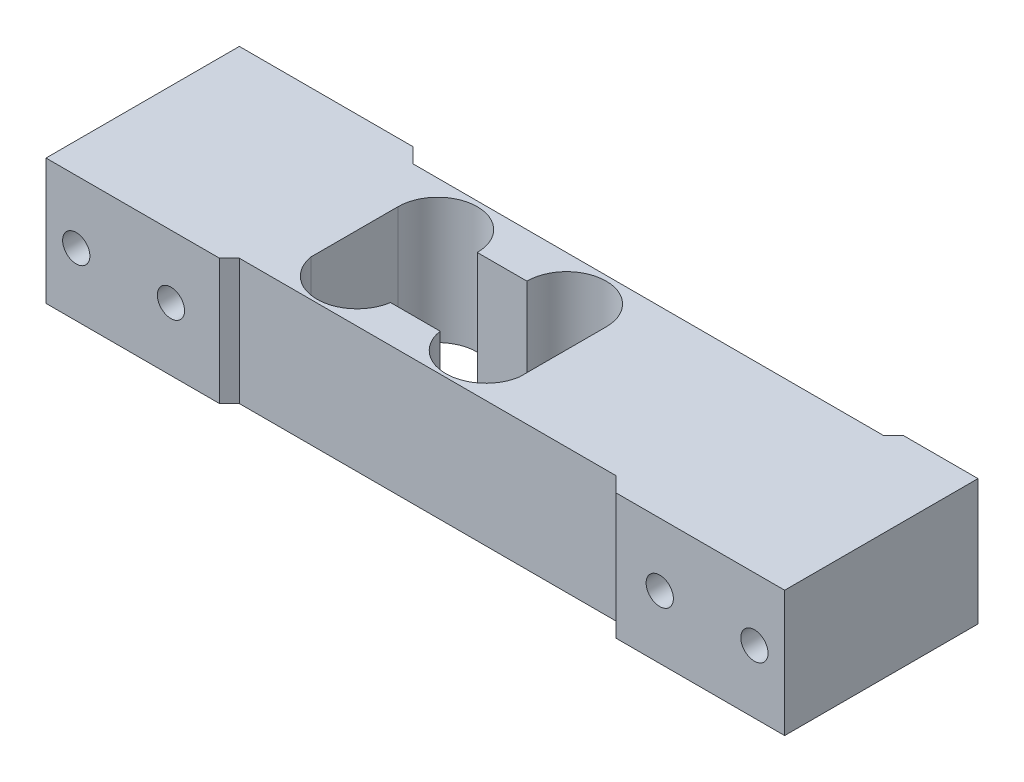
SolidWorks part; units mm, degrees
material "6063-T6"
ref_plane "Alzado" through (0, 0, 0) normal (0, 0, 1) x (1, 0, 0)
ref_plane "Planta" through (0, 0, 0) normal (0, 1, 0) x (1, 0, 0)
ref_plane "Vista lateral" through (0, 0, 0) normal (1, 0, 0) x (0, 0, -1)
sketch "Croquis1" plane through (0, 0, 0) normal (0, 1, 0) x (1, 0, 0)
  line L1 (-75, 20) -> (75, 20)
  line L2 (-75, 20) -> (-75, -20)
  line L3 (-75, -20) -> (75, -20)
  line L4 (75, 20) -> (75, -20)
  line L5 (-75, 20) -> (75, -20) construction
  line L6 (-75, -20) -> (75, 20) construction
  point P0 (0, 0)
  dimension "D1" = 40
  dimension "D2" = 150
extrude "Saliente-Extruir1" add sketch "Croquis1" along normal blind 25.4
sketch "Croquis2" plane through (0, 25.4, 0) normal (0, 1, 0) x (1, 0, 0)
  line L0 (-42, 20) -> (-42, 17)
  line L1 (75, 20) -> (-75, 20) construction
  line L2 (-42, 17) -> (61, 17)
  line L3 (61, 17) -> (61, 19)
  line L4 (60, 20) -> (-42, 20)
  line L5 (43, -20) -> (43, -17)
  line L6 (-75, -20) -> (75, -20) construction
  line L7 (43, -17) -> (-41, -17)
  line L8 (-41, -17) -> (-41, -19)
  line L9 (-41, -19) -> (-75, -19)
  line L10 (-75, 20) -> (-75, -20) construction
  line L11 (-75, -19) -> (-75, -20)
  line L12 (-75, -20) -> (43, -20)
  line L13 (75, -20) -> (75, 20) construction
  line L14 (61, 19) -> (75, 19)
  line L15 (75, 19) -> (75, 20)
  line L16 (75, 20) -> (60, 20)
  point P19 (-41, -18)
  dimension "D1" = 32
  dimension "D2" = 14
  dimension "D3" = 3
  dimension "D4" = 1
  dimension "D5" = 34
  dimension "D6" = 2
  dimension "D7" = 33
  dimension "D8" = 3
  dimension "D9" = 1
extrude "Cortar-Extruir1" cut sketch "Croquis2" against normal through all
chamfer "Chaflán1" distance 5 angle 45 2 edges at (43, 12.7, 17) (-42, 12.7, -17)
chamfer "Chaflán2" distance 3 angle 45 2 edges at (-41, 12.7, 17) (61, 12.7, -17)
sketch "Croquis3" plane through (0, 25.4, 0) normal (0, 1, 0) x (1, 0, 0)
  line L0 (-31, 17) -> (-31, -17) construction
  line L1 (-37, 17) -> (58, 17) construction
  line L2 (38, -17) -> (-38, -17) construction
  line L3 (11, 17) -> (11, -17) construction
  line L4 (-10, 17) -> (-10, -17) construction
  line L5 (-75, 20) -> (-75, -19) construction
  line L6 (-75, 8) -> (75, 8) construction
  line L7 (75, -20) -> (75, 19) construction
  line L8 (-75, -9.5) -> (75, -9.5) construction
  line L9 (-40, 20) -> (-75, 20) construction
  line L10 (-15, 8) -> (-5, 8)
  line L11 (-15, -9.5) -> (-5, -9.5)
  line L20 (-23, 8) -> (-23, -8.2527) construction
  line L22 (-31, 8) -> (-31, -9.5)
  line L23 (3, -8.2527) -> (3, 8) construction
  line L25 (11, -9.5) -> (11, 8)
  arc A0 (-15, 8) -> (-31, 8) centre (-23, 8) ccw
  arc A1 (-31, -9.5) -> (-15, -9.5) centre (-23, -8.2527) ccw
  arc A2 (-5, -9.5) -> (11, -9.5) centre (3, -8.2527) ccw
  arc A3 (11, 8) -> (-5, 8) centre (3, 8) ccw
  point P23 (-10, 8)
  point P26 (-10, -9.5)
  point P41 (-20.377, -0.75)
  point P48 (0.377, -0.75)
  dimension "D9" = 8
  dimension "D10" = 8
  dimension "D13" = 8.0966
  dimension "D1" = 65
  dimension "D2" = 86
  dimension "D3" = 44
  dimension "D4" = 12
  dimension "D5" = 17.5
  dimension "D6" = 10
  dimension "D7" = 5
  dimension "D8" = 5
  dimension "D11" = 16.2527
  dimension "D12" = 16.2527
extrude "Cortar-Extruir2" cut sketch "Croquis3" against normal through all
sketch "Croquis5" plane through (0, 0, -20) normal (0, 0, -1) x (-1, 0, 0)
  line L0 (75, 12.7) -> (40, 12.7) construction
  line L1 (75, 25.4) -> (75, 0) construction
  line L2 (40, 25.4) -> (40, 0) construction
  line L3 (68.9, 0) -> (68.9, 25.4) construction
  line L4 (40, 0) -> (75, 0) construction
  line L5 (40, 25.4) -> (75, 25.4) construction
  line L6 (49.8, 0) -> (49.8, 25.4) construction
  circle A0 centre (68.9, 12.7) radius 2.75
  circle A1 centre (49.8, 12.7) radius 2.75
  dimension "D3" = 5.5
  dimension "D1" = 6.1
  dimension "D2" = 19.1
extrude "Cortar-Extruir3" cut sketch "Croquis5" against normal blind 16
sketch "Croquis6" plane through (-75, 0, 0) normal (-1, 0, 0) x (0, 0, 1)
  line L0 (19, 12.7) -> (-20, 12.7) construction
  line L1 (19, 0) -> (19, 25.4) construction
  line L2 (-20, 25.4) -> (-20, 0) construction
  line L3 (9.05, 0) -> (9.05, 25.4) construction
  line L4 (-20, 0) -> (19, 0) construction
  line L5 (-20, 25.4) -> (19, 25.4) construction
  line L6 (-10.05, 0) -> (-10.05, 25.4) construction
  circle A0 centre (9.05, 12.7) radius 2.75
  circle A1 centre (-10.05, 12.7) radius 2.75
  dimension "D3" = 5.5
  dimension "D1" = 19.1
  dimension "D2" = 9.95
extrude "Cortar-Extruir4" cut sketch "Croquis6" against normal blind 16
sketch "Croquis7" plane through (0, 0, 19) normal (0, 0, 1) x (1, 0, 0)
  line L0 (-75, 12.7) -> (-40, 12.7) construction
  line L1 (-75, 0) -> (-75, 25.4) construction
  line L2 (-40, 0) -> (-40, 25.4) construction
  line L3 (-68.9, 25.4) -> (-68.9, 0) construction
  line L4 (-40, 25.4) -> (-75, 25.4) construction
  line L5 (-40, 0) -> (-75, 0) construction
  line L6 (-49.8, 25.4) -> (-49.8, 0) construction
  circle A0 centre (-68.9, 12.7) radius 2.75
  circle A1 centre (-49.8, 12.7) radius 2.75
  dimension "D3" = 5.5
  dimension "D1" = 19.1
  dimension "D2" = 6.1
extrude "Cortar-Extruir8" cut sketch "Croquis7" against normal blind 16
sketch "Croquis8" plane through (0, 0, 20) normal (0, 0, 1) x (1, 0, 0)
  line L0 (41, 12.7) -> (75, 12.7) construction
  line L1 (41, 25.4) -> (41, 0) construction
  line L2 (75, 25.4) -> (75, 0) construction
  line L3 (49.8, 25.4) -> (49.8, 0) construction
  line L4 (41, 25.4) -> (75, 25.4) construction
  line L5 (41, 0) -> (75, 0) construction
  line L6 (68.9, 25.4) -> (68.9, 0) construction
  circle A0 centre (49.8, 12.7) radius 2.75
  circle A1 centre (68.9, 12.7) radius 2.75
  dimension "D3" = 5.5
  dimension "D1" = 19.1
  dimension "D2" = 6.1
extrude "Cortar-Extruir9" cut sketch "Croquis8" against normal blind 16
